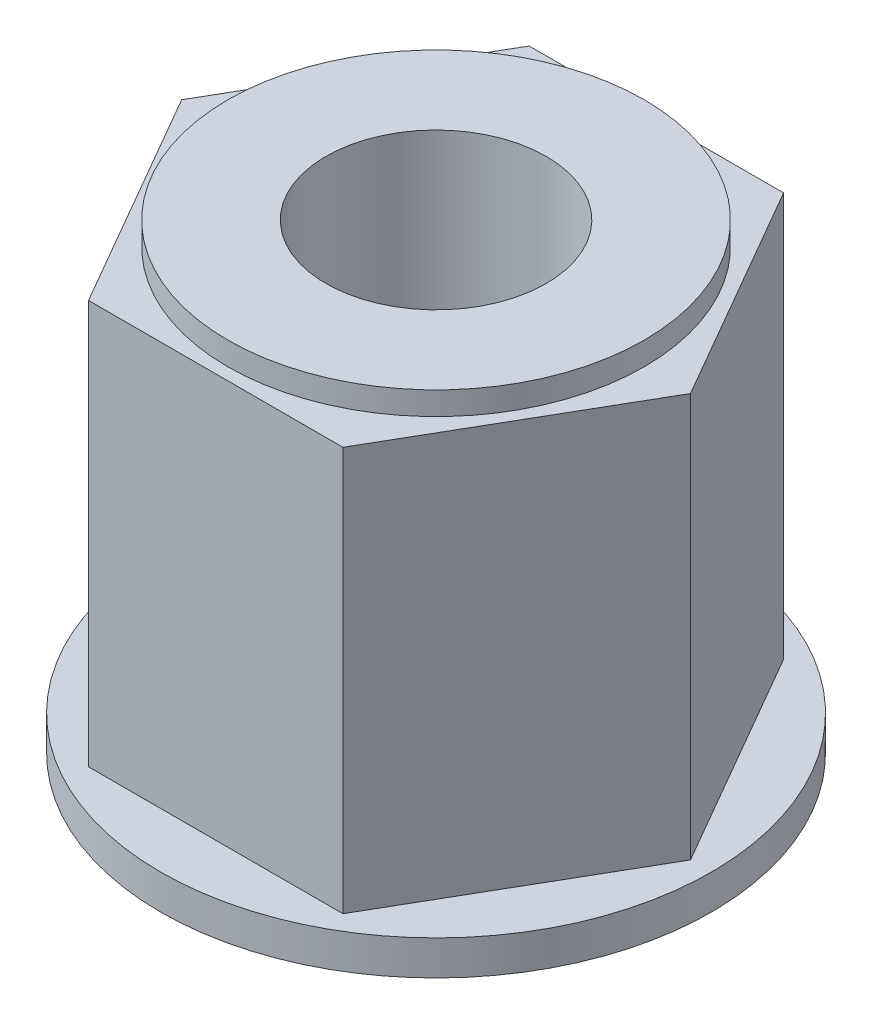
SolidWorks part; units mm, degrees
ref_plane "Front Plane" through (0, 0, 0) normal (0, 0, 1) x (1, 0, 0)
ref_plane "Top Plane" through (0, 0, 0) normal (0, 1, 0) x (1, 0, 0)
ref_plane "Right Plane" through (0, 0, 0) normal (1, 0, 0) x (0, 0, -1)
ref_plane "Plane1" through (0, 0, 0) normal (0, 0, -1) x (-1, 0, 0)
sketch "Sketch1" plane through (0, 0, 0) normal (0, 0, -1) x (-1, 0, 0)
  line L0 (-11.9062, -1.5) -> (0, -1.5)
  line L1 (0, -1.5) -> (0, 0)
  line L2 (0, 0) -> (-11.9062, 0)
  line L3 (-11.9062, 0) -> (-11.9062, -1.5)
  line L4 (0, -1.5) -> (0, 0) construction
revolve "Revolve1" add sketch "Sketch1" angle 360 about L4 reverse direction yes
sketch "Sketch2" plane through (0, 0, 0) normal (0, 1, 0) x (-1, 0, 0)
  line L0 (10.9985, 0) -> (5.4993, -9.525)
  line L1 (5.4993, -9.525) -> (-5.4993, -9.525)
  line L2 (-5.4993, -9.525) -> (-10.9985, 0)
  line L3 (-10.9985, 0) -> (-5.4993, 9.525)
  line L4 (-5.4993, 9.525) -> (5.4993, 9.525)
  line L5 (5.4993, 9.525) -> (10.9985, 0)
extrude "Boss-Extrude1" add sketch "Sketch2" along normal blind 17.4625
sketch "Sketch3" plane through (0, 0, 0) normal (0, 0, 1) x (1, 0, 0)
  line L0 (9, 18.4625) -> (0, 18.4625)
  line L1 (0, 18.4625) -> (0, 17.4625)
  line L2 (0, 17.4625) -> (9, 17.4625)
  line L3 (9, 17.4625) -> (9, 18.4625)
  line L4 (0, 18.4625) -> (0, 17.4625) construction
revolve "Revolve2" add sketch "Sketch3" angle 360 about L4 reverse direction yes
hole_wizard "M8 Clearance Hole1" positions "Sketch5" profile "Sketch4" hole size "M8" standard "ANSI Metric"
sketch "Sketch5" plane through (0, -1.5, 0) normal (0, -1, 0) x (-1, 0, 0)
  point P0 (0, 0)
sketch "Sketch4" plane through (0, -1.5, 0) normal (1, 0, 0) x (0, 0, -1)
  line L0 (0, 0) -> (0, 19.9625)
  line L1 (0, 19.9625) -> (4.7625, 19.9625)
  line L2 (4.7625, 19.9625) -> (4.7625, 0)
  line L5 (4.7625, 0) -> (0, 0)
  line L11 (0, -6.35) -> (0, 107.95) construction
  dimension "Thru Hole Dia." = 9.525
  dimension "Thru Hole Depth" = 19.9625
